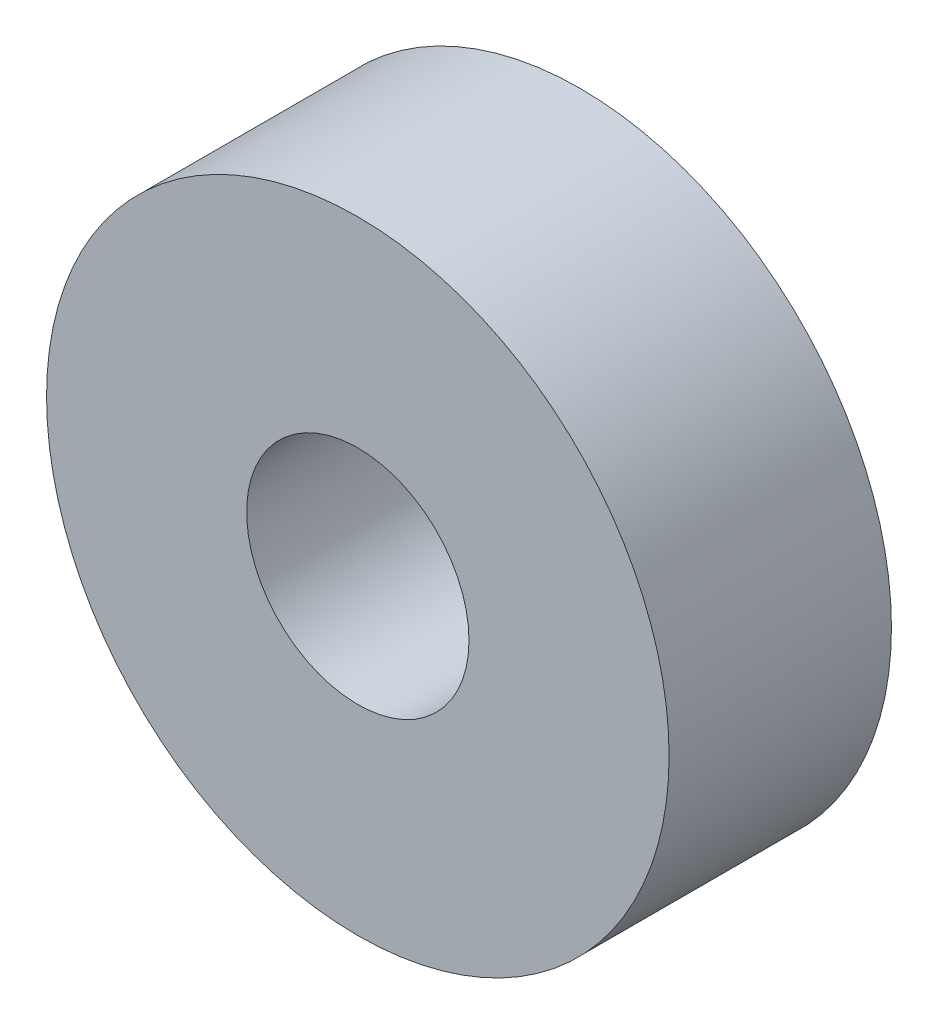
SolidWorks part; units mm, degrees
ref_plane "Front Plane" through (0, 0, 0) normal (0, 0, 1) x (1, 0, 0)
ref_plane "Top Plane" through (0, 0, 0) normal (0, 1, 0) x (1, 0, 0)
ref_plane "Right Plane" through (0, 0, 0) normal (1, 0, 0) x (0, 0, -1)
ref_plane "Plane1" through (0, 0, 5) normal (0, 0, 1) x (1, 0, 0)
sketch "Sketch1" plane through (0, 0, 5) normal (0, 0, 1) x (1, 0, 0)
  circle A0 centre (0, 0) radius 7
extrude "Boss-Extrude1" add sketch "Sketch1" against normal blind 5
hole_wizard "Ø5.0 (5) Diameter Hole1" positions "Sketch3" profile "Sketch2" hole size "Ø5.0" standard "ANSI Metric"
sketch "Sketch3" plane through (0, 0, 5) normal (0, 0, 1) x (1, 0, 0)
  point P0 (0, 0)
sketch "Sketch2" plane through (0, 0, 5) normal (1, 0, 0) x (0, -1, 0)
  line L0 (0, 0) -> (0, 5)
  line L1 (0, 5) -> (2.5, 5)
  line L2 (2.5, 5) -> (2.5, 0)
  line L5 (2.5, 0) -> (0, 0)
  line L11 (0, -6.35) -> (0, 107.95) construction
  dimension "Thru Hole Dia." = 5
  dimension "Thru Hole Depth" = 5
ref_axis "Axis1" through (0, 0, -2.1278) along (0, 0, 1)
ref_plane "Plane2" through (0, 0, 2.5) normal (0, 0, -1) x (-1, 0, 0)
